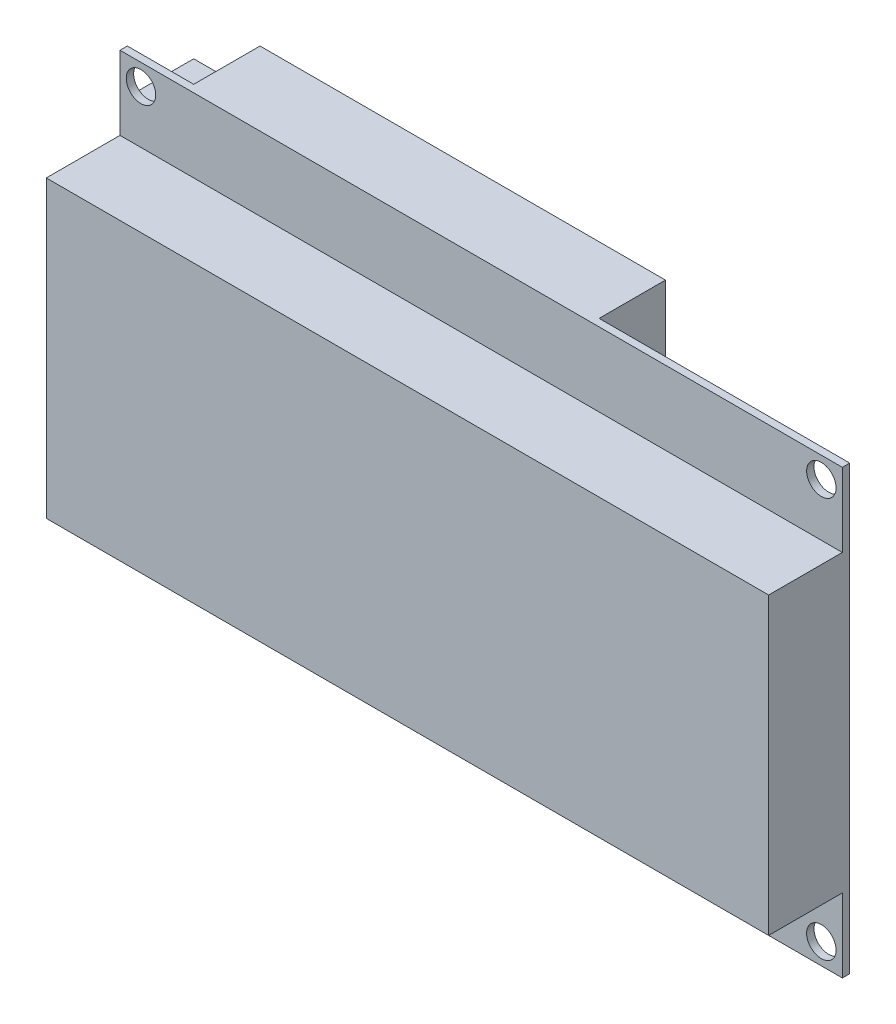
SolidWorks part; units mm, degrees
ref_plane "Plan de face" through (0, 0, 0) normal (0, 0, 1) x (1, 0, 0)
ref_plane "Plan de dessus" through (0, 0, 0) normal (0, 1, 0) x (1, 0, 0)
ref_plane "Plan de droite" through (0, 0, 0) normal (1, 0, 0) x (0, 0, -1)
sketch "Esquisse1" plane through (0, 0, 0) normal (0, 0, 1) x (1, 0, 0)
  line L1 (0, 0) -> (98, 0)
  line L2 (0, 0) -> (0, 60)
  line L3 (0, 60) -> (98, 60)
  line L4 (98, 0) -> (98, 60)
  dimension "D1" = 98
  dimension "D2" = 60
extrude "Boss.-Extru.1" add sketch "Esquisse1" against normal blind 11
sketch "Esquisse2" plane through (0, 0, 0) normal (0, 0, 1) x (1, 0, 0)
  line L0 (0, 60) -> (0, 0) construction
  line L1 (0, 50) -> (98, 50)
  line L3 (0, 10) -> (98, 10)
  line L5 (98, 0) -> (98, 60) construction
  line L6 (98, 60) -> (0, 60) construction
  line L7 (0, 0) -> (98, 0) construction
  line L8 (0, 0) -> (98, 0)
  line L9 (98, 0) -> (98, 10)
  line L10 (0, 60) -> (0, 50)
  line L11 (98, 60) -> (0, 60)
  line L12 (98, 50) -> (98, 60)
  line L13 (0, 10) -> (0, 0)
  dimension "D1" = 10
  dimension "D2" = 10
extrude "Enlèv. mat.-Extru.1" cut sketch "Esquisse2" against normal blind 10
sketch "Esquisse3" plane through (0, 0, -11) normal (0, 0, -1) x (-1, 0, 0)
  line L0 (0, 60) -> (0, 0) construction
  line L1 (-9, 60) -> (-64, 60)
  line L2 (-9, 60) -> (-9, 54)
  line L3 (-9, 40) -> (-64, 40)
  line L4 (-64, 60) -> (-64, 40)
  line L5 (-98, 60) -> (0, 60) construction
  line L6 (-9, 54) -> (0, 54)
  line L8 (-9, 45) -> (0, 45)
  line L9 (0, 54) -> (0, 45)
  line L10 (-9, 45) -> (-9, 40)
  dimension "D1" = 55
  dimension "D2" = 20
  dimension "D3" = 9
  dimension "D4" = 6
  dimension "D5" = 5
extrude "Boss.-Extru.2" add sketch "Esquisse3" along normal blind 9
sketch "Esquisse4" plane through (0, 0, -10) normal (0, 0, 1) x (1, 0, 0)
  line L0 (98, 60) -> (0, 60) construction
  line L1 (0, 60) -> (0, 50) construction
  circle A0 centre (2.85, 57.15) radius 2.85
  circle A1 centre (2.85, 57.15) radius 2
  circle A2 centre (95.15, 57.15) radius 2.85
  circle A3 centre (95.15, 57.15) radius 2
  circle A4 centre (95.15, 2.85) radius 2.85
  circle A5 centre (95.15, 2.85) radius 2
  circle A6 centre (2.85, 2.85) radius 2.85
  circle A7 centre (2.85, 2.85) radius 2
  dimension "D2" = 4
  dimension "D1" = 0.85
  dimension "D3" = 2
  dimension "D4" = 2
extrude "Enlèv. mat.-Extru.2" cut sketch "Esquisse4" against normal up to next contours A1 | A7 | A3 | A5
